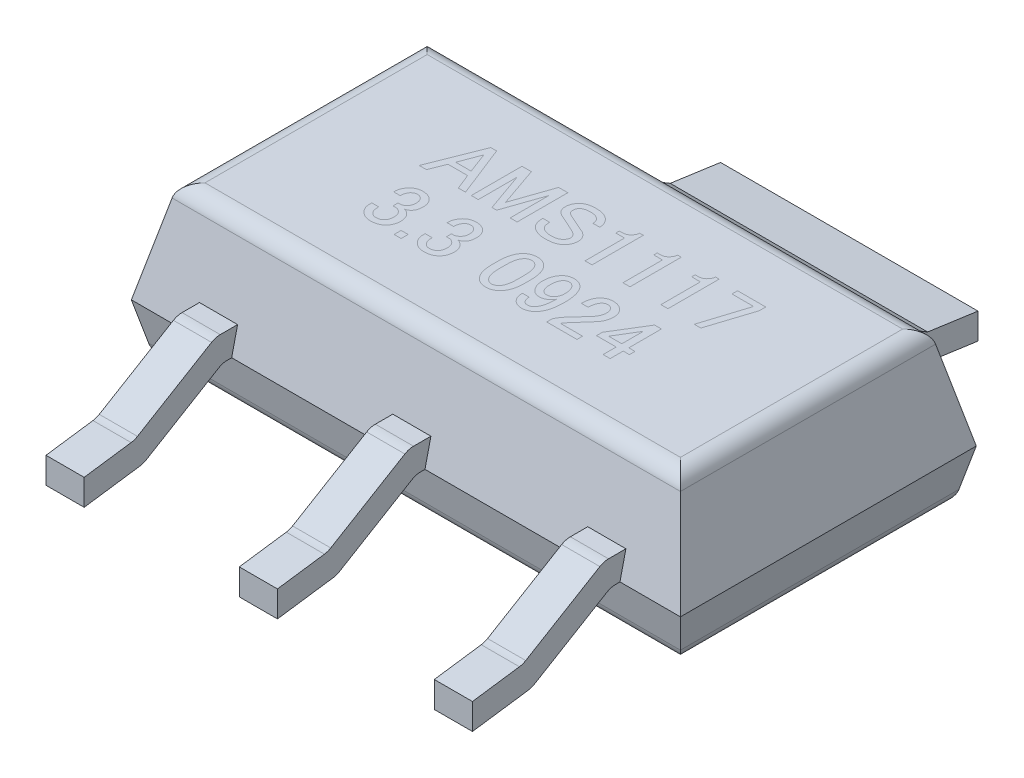
SolidWorks part; units mm, degrees
ref_plane "Front Plane" through (0, 0, 0) normal (0, 0, 1) x (1, 0, 0)
ref_plane "Top Plane" through (0, 0, 0) normal (0, 1, 0) x (1, 0, 0)
ref_plane "Right Plane" through (0, 0, 0) normal (1, 0, 0) x (0, 0, -1)
sketch "Sketch5" plane through (0, 0, 0) normal (0, 1, 0) x (1, 0, 0)
  line L1 (-3.2525, 1.7525) -> (3.2525, 1.7525)
  line L2 (-3.2525, 1.7525) -> (-3.2525, -1.7525)
  line L3 (-3.2525, -1.7525) -> (3.2525, -1.7525)
  line L4 (3.2525, 1.7525) -> (3.2525, -1.7525)
  line L5 (-3.2525, 1.7525) -> (3.2525, -1.7525) construction
  line L6 (-3.2525, -1.7525) -> (3.2525, 1.7525) construction
  point P0 (0, 0)
  dimension "D1" = 3.505
  dimension "D2" = 6.505
extrude "Boss-Extrude1" add sketch "Sketch5" along normal blind 1.2 draft 13
extrude "Boss-Extrude2" add sketch "Sketch5<2>" against normal blind 0.6 draft 13
sketch "Sketch5<2>" plane through (0, 0, 0) normal (0, 1, 0) x (1, 0, 0) same geometry as "Sketch5"
sketch "Sketch6" plane through (0, 0, 0) normal (1, 0, 0) x (0, 0, -1)
  line L0 (-2.9036, -0.2693) -> (-3.5, -0.3531)
  line L1 (-3.5, -0.6611) -> (0, -0.6611) construction
  line L2 (-2.8, -0.5627) -> (-3.5, -0.6611)
  line L3 (0, 0) -> (0, -0.6611) construction
  line L4 (-1.614, -0.6) -> (1.614, -0.6) construction
  line L5 (-2.9036, -0.2693) -> (-1.9433, 0.305)
  line L6 (-1.9433, 0.305) -> (-1.6821, 0.305)
  line L7 (-2.8, -0.5627) -> (-1.8591, 0)
  line L8 (-1.8591, 0) -> (-1.7525, 0)
  line L9 (-1.9433, 0.305) -> (-1.7525, 0.305) construction
  line L10 (-3.5, -0.6611) -> (-3.5, -0.3531)
  line L11 (-1.4755, 1.2) -> (-1.7525, 0) construction
  line L12 (-1.6821, 0.305) -> (-1.7525, 0)
  line L13 (-2.9036, -0.2693) -> (-3.5424, -0.3591) construction
  dimension "D1" = 8
  dimension "D2" = 0.0611
  dimension "D3" = 3.5
  dimension "D4" = 0.7
  dimension "D5" = 0.305
extrude "Boss-Extrude3" add sketch "Sketch6" along normal mid plane 0.452
mirror "Mirror1" about plane through (0, 0, 0) normal (0, 0, 1) of "Boss-Extrude3"
sketch "Sketch7" plane through (0, 0, 0) normal (1, 0, 0) x (0, 0, -1)
  line L8 (2.9036, -0.2693) -> (1.9433, 0.305)
  line L9 (1.9433, 0.305) -> (1.6821, 0.305)
  line L10 (1.6821, 0.305) -> (1.7525, 0)
  line L11 (1.7525, 0) -> (1.8591, 0)
  line L12 (1.8591, 0) -> (2.8, -0.5627)
  line L13 (2.8, -0.5627) -> (3.5, -0.6611)
  line L14 (3.5, -0.6611) -> (3.5, -0.3531)
  line L15 (3.5, -0.3531) -> (2.9036, -0.2693)
  line L16 (2.9036, -0.2693) -> (1.9433, 0.305)
  line L17 (1.9433, 0.305) -> (1.6821, 0.305)
  line L18 (1.6821, 0.305) -> (1.7525, 0)
  line L19 (1.7525, 0) -> (1.8591, 0)
  line L20 (1.8591, 0) -> (2.8, -0.5627)
  line L21 (2.8, -0.5627) -> (3.5, -0.6611)
  line L22 (3.5, -0.6611) -> (3.5, -0.3531)
  line L23 (3.5, -0.3531) -> (2.9036, -0.2693)
  dimension "D1" = 0
extrude "Boss-Extrude4" add sketch "Sketch7" along normal mid plane 3.05
ref_plane "Plane4" through (-2.29, 0, 0) normal (-1, 0, 0) x (0, 0, 1)
ref_plane "Plane5" through (2.31, 0, 0) normal (1, 0, 0) x (0, 0, -1)
sketch "Sketch8" plane through (-2.29, 0, 0) normal (-1, 0, 0) x (0, 0, 1)
  line L8 (1.8591, 0) -> (2.8, -0.5627)
  line L9 (2.8, -0.5627) -> (3.5, -0.6611)
  line L10 (3.5, -0.6611) -> (3.5, -0.3531)
  line L11 (3.5, -0.3531) -> (2.9036, -0.2693)
  line L12 (2.9036, -0.2693) -> (1.9433, 0.305)
  line L13 (1.9433, 0.305) -> (1.6821, 0.305)
  line L14 (1.6821, 0.305) -> (1.7525, 0)
  line L15 (1.7525, 0) -> (1.8591, 0)
  line L16 (1.8591, 0) -> (2.8, -0.5627)
  line L17 (2.8, -0.5627) -> (3.5, -0.6611)
  line L18 (3.5, -0.6611) -> (3.5, -0.3531)
  line L19 (3.5, -0.3531) -> (2.9036, -0.2693)
  line L20 (2.9036, -0.2693) -> (1.9433, 0.305)
  line L21 (1.9433, 0.305) -> (1.6821, 0.305)
  line L22 (1.6821, 0.305) -> (1.7525, 0)
  line L23 (1.7525, 0) -> (1.8591, 0)
  dimension "D1" = 0
extrude "Boss-Extrude5" add sketch "Sketch8" along normal mid plane 0.452
sketch "Sketch9" plane through (2.31, 0, 0) normal (1, 0, 0) x (0, 0, -1)
  line L8 (-2.8, -0.5627) -> (-1.8591, 0)
  line L9 (-3.5, -0.6611) -> (-2.8, -0.5627)
  line L10 (-3.5, -0.3531) -> (-3.5, -0.6611)
  line L11 (-2.9036, -0.2693) -> (-3.5, -0.3531)
  line L12 (-1.9433, 0.305) -> (-2.9036, -0.2693)
  line L13 (-1.6821, 0.305) -> (-1.9433, 0.305)
  line L14 (-1.7525, 0) -> (-1.6821, 0.305)
  line L15 (-1.8591, 0) -> (-1.7525, 0)
  line L16 (-2.8, -0.5627) -> (-1.8591, 0)
  line L17 (-3.5, -0.6611) -> (-2.8, -0.5627)
  line L18 (-3.5, -0.3531) -> (-3.5, -0.6611)
  line L19 (-2.9036, -0.2693) -> (-3.5, -0.3531)
  line L20 (-1.9433, 0.305) -> (-2.9036, -0.2693)
  line L21 (-1.6821, 0.305) -> (-1.9433, 0.305)
  line L22 (-1.7525, 0) -> (-1.6821, 0.305)
  line L23 (-1.8591, 0) -> (-1.7525, 0)
  dimension "D1" = 0
extrude "Boss-Extrude6" add sketch "Sketch9" along normal mid plane 0.452
fillet "Fillet1" radius 0.2 8 edges at (-2.9755, 1.2, 0) (0, 1.2, -1.4755) (0, 1.2, 1.4755) (2.9755, 1.2, 0) (-3.114, -0.6, 0) (0, -0.6, -1.614) (0, -0.6, 1.614) (3.114, -0.6, 0)
fillet "Fillet2" radius 0.2 14 edges at (0, -0.5627, -2.8) (0, 0, -1.8591) (-2.29, -0.5627, 2.8) (-2.29, 0, 1.8591) (0, -0.5627, 2.8) (0, 0, 1.8591) (2.31, -0.5627, 2.8) (2.31, 0, 1.8591) (-2.29, 0.305, 1.9433) (-2.29, -0.2693, 2.9036) (0, 0.305, 1.9433) (0, -0.2693, 2.9036) (2.31, -0.2693, 2.9036) (2.31, 0.305, 1.9433)
ref_plane "Plane6" through (0, 5.8, 0) normal (0, 1, 0) x (1, 0, 0)
sketch "Sketch10" plane through (0, 5.8, 0) normal (0, 1, 0) x (1, 0, 0)
  line L0 (-2.2259, 0.1205) -> (2.3253, 0.1205) construction
  line L1 (-2.2035, -0.7302) -> (2.026, -0.7302) construction
  text T0 "AMS1117" font "MS UI Gothic" height in points 2
  text T1 "3.3 0924" font "MS UI Gothic" height in points 2
  point P7 (0.0497, 0.1205)
split line "Split Line1"
